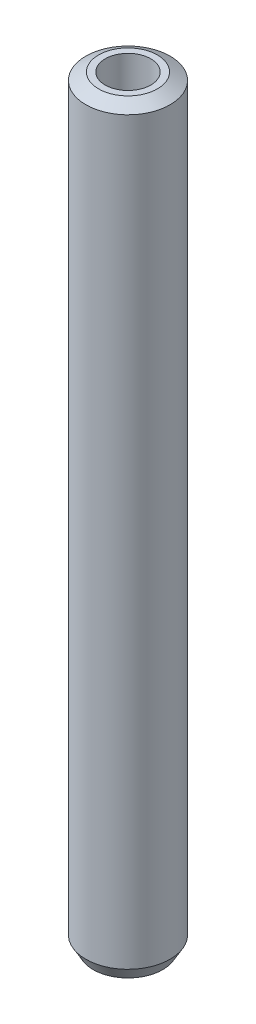
SolidWorks part; units mm, degrees
ref_plane "Front Plane" through (0, 0, 0) normal (0, 0, 1) x (1, 0, 0)
ref_plane "Top Plane" through (0, 0, 0) normal (0, 1, 0) x (1, 0, 0)
ref_plane "Right Plane" through (0, 0, 0) normal (1, 0, 0) x (0, 0, -1)
sketch "Sketch1" plane through (0, 0, 0) normal (0, 1, 0) x (1, 0, 0)
  circle A0 centre (0, 0) radius 32.5
  dimension "SHAFT_OD" = 65
extrude "Boss-Extrude1" add sketch "Sketch1" along normal blind 586.1432
sketch "Sketch2" plane through (0, 0, 0) normal (0, 1, 0) x (1, 0, 0)
  circle A0 centre (0, 0) radius 17.5744
  dimension "BORE_D" = 35.1488
extrude "Cut-Extrude1" cut sketch "Sketch2" along normal through all
chamfer "Chamfer1" distance 5.6708 angle 60 2 edges at (0, 586.1432, 32.5) (0, 0, 32.5) first distance on face at (0, 586.1432, 32.5) first distance on face at (0, 0, 17.5744)
